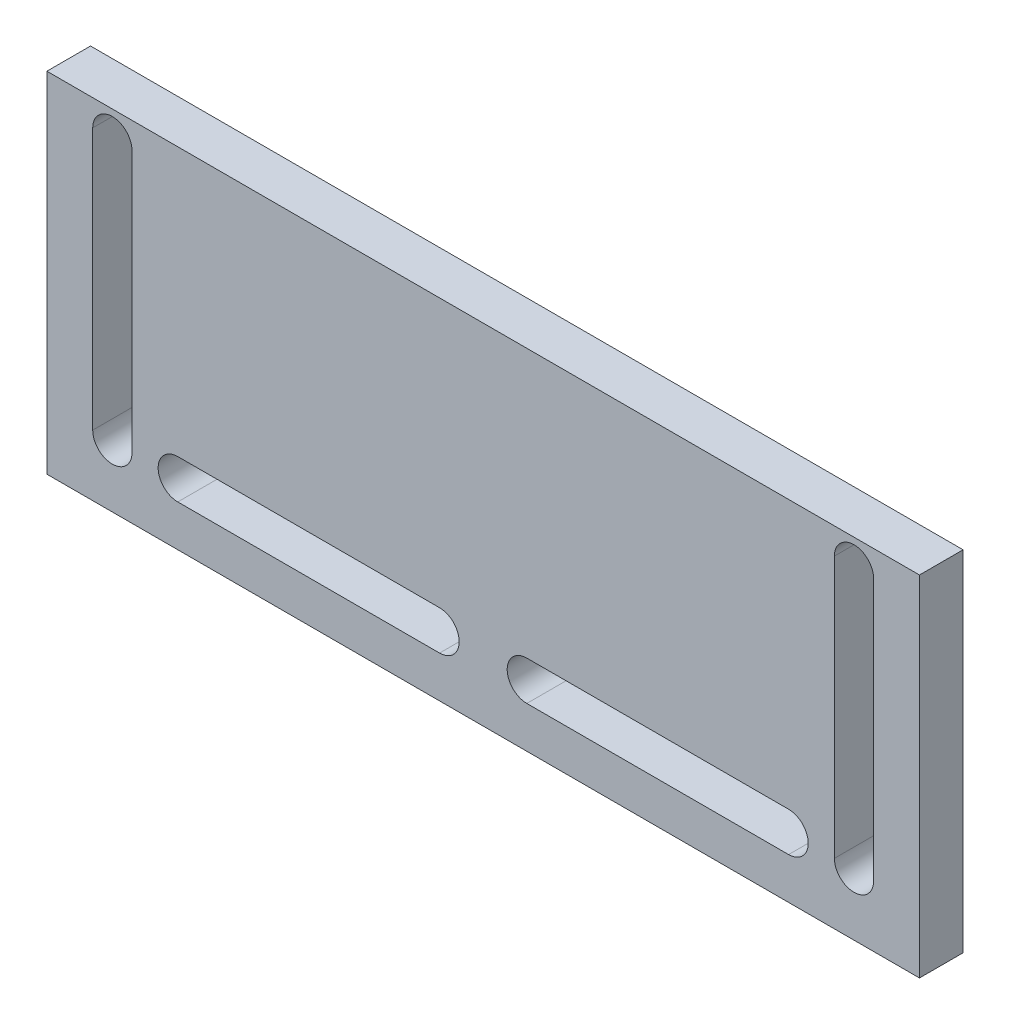
SolidWorks part; units mm, degrees
ref_plane "Front Plane" through (0, 0, 0) normal (0, 0, 1) x (1, 0, 0)
ref_plane "Top Plane" through (0, 0, 0) normal (0, 1, 0) x (1, 0, 0)
ref_plane "Right Plane" through (0, 0, 0) normal (1, 0, 0) x (0, 0, -1)
sketch "Sketch1" plane through (0, 0, 0) normal (0, 0, 1) x (1, 0, 0)
  line L1 (50, -20) -> (-50, -20)
  line L2 (50, -20) -> (50, 20)
  line L3 (50, 20) -> (-50, 20)
  line L4 (-50, -20) -> (-50, 20)
  line L5 (50, -20) -> (-50, 20) construction
  line L6 (50, 20) -> (-50, -20) construction
  point P0 (0, 0)
  dimension "D1" = 40
  dimension "D2" = 100
extrude "Boss-Extrude1" add sketch "Sketch1" along normal blind 5
sketch "Sketch2" plane through (0, 0, 5) normal (0, 0, 1) x (1, 0, 0)
  line L0 (-42.5, 17) -> (-42.5, -13) construction
  line L1 (-40.25, 17) -> (-40.25, -13)
  line L2 (-35, -13) -> (-5, -13) construction
  line L3 (-44.75, 17) -> (-44.75, -13)
  line L7 (42.5, 17) -> (42.5, -13) construction
  line L8 (44.75, 17) -> (44.75, -13)
  line L9 (40.25, 17) -> (40.25, -13)
  line L11 (5, -13) -> (35, -13) construction
  line L12 (5, -10.75) -> (35, -10.75)
  line L13 (5, -15.25) -> (35, -15.25)
  line L14 (-50, -20) -> (50, -20) construction
  line L15 (-50, 20) -> (-50, -20) construction
  line L16 (50, -20) -> (50, 20) construction
  line L17 (-35, -10.75) -> (-5, -10.75)
  line L18 (-35, -15.25) -> (-5, -15.25)
  arc A8 (-40.25, 17) -> (-44.75, 17) centre (-42.5, 17) ccw
  arc A9 (-44.75, -13) -> (-40.25, -13) centre (-42.5, -13) ccw
  arc A10 (44.75, 17) -> (40.25, 17) centre (42.5, 17) ccw
  arc A11 (40.25, -13) -> (44.75, -13) centre (42.5, -13) ccw
  arc A14 (5, -10.75) -> (5, -15.25) centre (5, -13) ccw
  arc A15 (35, -15.25) -> (35, -10.75) centre (35, -13) ccw
  arc A16 (-35, -10.75) -> (-35, -15.25) centre (-35, -13) ccw
  arc A17 (-5, -15.25) -> (-5, -10.75) centre (-5, -13) ccw
  point P2 (-42.5, 2)
  point P7 (-20, -13)
  point P10 (42.5, 2)
  point P21 (20, -13)
  point P28 (-21.9139, -14.7792)
  point P33 (0, 0)
  point P36 (-6.4361, -12.675)
  point P37 (0, 0)
  point P38 (0, 0)
  point P39 (-5.0291, -15.25)
  point P40 (0, 0)
  point P41 (0, 0)
  point P42 (0, 0)
  point P43 (0, 0)
  point P44 (0, 0)
  point P45 (0, 0)
  point P46 (0, 0)
  point P47 (0, 0)
  point P48 (0, 0)
  dimension "D7" = 30
  dimension "D1" = 30
  dimension "D2" = 4.5
  dimension "D3" = 30
  dimension "D4" = 4.5
  dimension "D5" = 30
  dimension "D6" = 4.5
  dimension "D8" = 4.5
  dimension "D9" = 7
  dimension "D10" = 7
  dimension "D11" = 7.5
  dimension "D12" = 7.5
  dimension "D13" = 7.5
  dimension "D14" = 7.5
extrude "Cut-Extrude1" cut sketch "Sketch2" against normal blind 5 contours L1 A9 L3 A8
extrude "Cut-Extrude2" cut sketch "Sketch2<3>" against normal blind 5 contours L17 A17 L18 A16
sketch "Sketch2<3>" plane through (0, 0, 5) normal (0, 0, 1) x (1, 0, 0) same geometry as "Sketch2"
extrude "Cut-Extrude3" cut sketch "Sketch2<4>" against normal blind 5 contours L12 A15 L13 A14
sketch "Sketch2<4>" plane through (0, 0, 5) normal (0, 0, 1) x (1, 0, 0) same geometry as "Sketch2"
extrude "Cut-Extrude4" cut sketch "Sketch2<5>" against normal blind 5 contours L9 A11 L8 A10
sketch "Sketch2<5>" plane through (0, 0, 5) normal (0, 0, 1) x (1, 0, 0) same geometry as "Sketch2"
